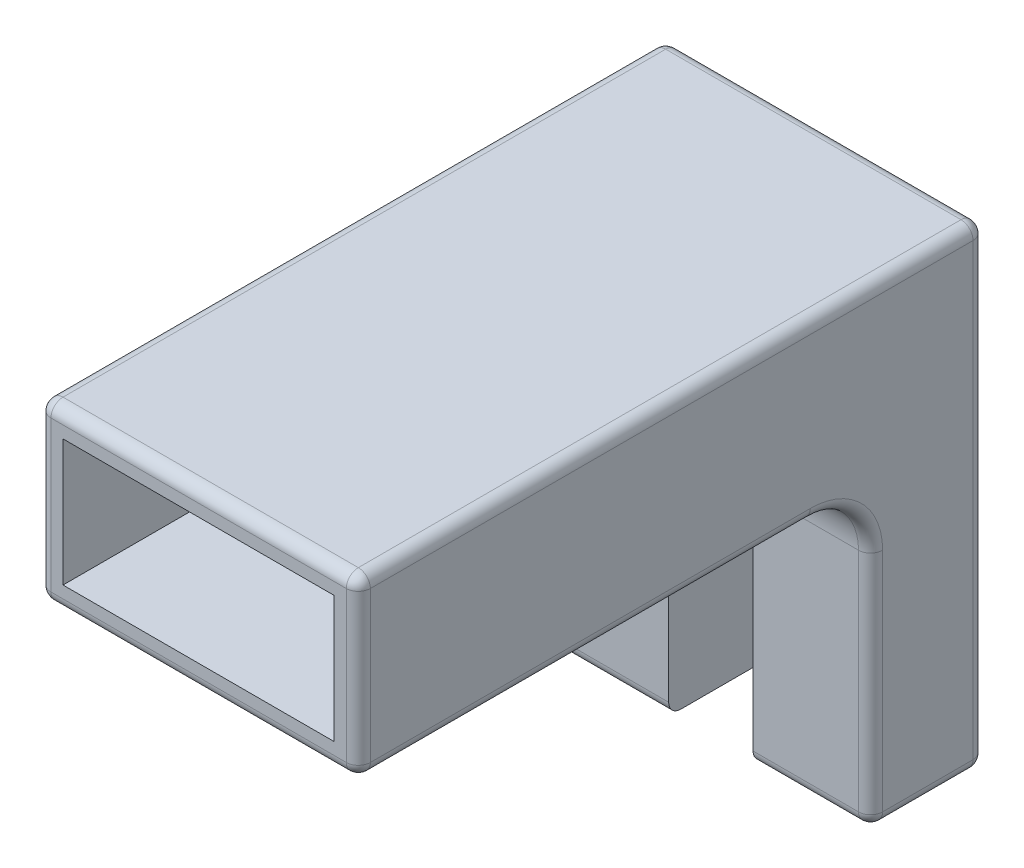
SolidWorks part; units mm, degrees
ref_plane "正面" through (0, 0, 0) normal (0, 0, 1) x (1, 0, 0)
ref_plane "平面" through (0, 0, 0) normal (0, 1, 0) x (1, 0, 0)
ref_plane "右側面" through (0, 0, 0) normal (1, 0, 0) x (0, 0, -1)
sketch "ｽｹｯﾁ2" plane through (0, 0, 0) normal (0, 0, 1) x (1, 0, 0)
  line L1 (0, 0) -> (26.5, 0)
  line L2 (0, 0) -> (0, 14.5)
  line L3 (0, 14.5) -> (26.5, 14.5)
  line L4 (26.5, 0) -> (26.5, 14.5)
  dimension "D1" = 14.5
  dimension "D2" = 26.5
extrude "ﾎﾞｽ - 押し出し1" add sketch "ｽｹｯﾁ2" along normal blind 52
sketch "ｽｹｯﾁ6" plane through (0, 0, 52) normal (0, 0, 1) x (1, 0, 0)
  line L0 (26.5, 14.5) -> (0, 14.5) construction
  line L1 (2, 12.5) -> (24.5, 12.5)
  line L2 (2, 12.5) -> (2, 2)
  line L3 (2, 2) -> (24.5, 2)
  line L4 (24.5, 12.5) -> (24.5, 2)
  line L5 (0, 14.5) -> (0, 0) construction
  dimension "D1" = 10.5
  dimension "D2" = 22.5
  dimension "D3" = 2
  dimension "D4" = 2
extrude "ｶｯﾄ - 押し出し1" cut sketch "ｽｹｯﾁ6" against normal blind 49
sketch "ｽｹｯﾁ7" plane through (0, 0, 0) normal (0, -1, 0) x (1, 0, 0)
  line L0 (26.5, 52) -> (26.5, 0) construction
  line L1 (0, 0) -> (26.5, 0)
  line L2 (0, 0) -> (0, 9.5)
  line L3 (0, 9.5) -> (26.5, 9.5)
  line L4 (26.5, 0) -> (26.5, 9.5)
  dimension "D1" = 9.5
extrude "ﾎﾞｽ - 押し出し2" add sketch "ｽｹｯﾁ7" along normal blind 24.8
fillet "ﾌｨﾚｯﾄ1" radius 5 1 edges at (13.25, 0, 9.5)
fillet "ﾌｨﾚｯﾄ2" radius 1 1 edges at (26.5, 14.5, 26)
fillet "ﾌｨﾚｯﾄ4" radius 1 7 edges at (12.75, 14.5, 0) (26.2071, 14.2071, 0) (26.5, -5.65, 0) (26.5, -24.8, 4.75) (26.5, -14.9, 9.5) (26.5, -1.4645, 10.9645) (26.5, 0, 33.25)
fillet "ﾌｨﾚｯﾄ5" radius 1 11 edges at (0, 14.2071, 0.2929) (26.2071, -24.5071, 0.2929) (26.2071, -24.5071, 9.2071) (0, 14.5, 26.5) (0, -5.65, 0) (0, 0, 33.25) (0, -1.4645, 10.9645) (0, -14.9, 9.5) (0, -24.8, 4.75) (12.75, -24.8, 0) (12.75, -24.8, 9.5)
fillet "ﾌｨﾚｯﾄ6" radius 1 8 edges at (26.2071, 0.2929, 52) (26.2071, 14.2071, 52) (0.2929, 14.2071, 52) (0.2929, 0.2929, 52) (26.5, 7.25, 52) (13.25, 14.5, 52) (13.25, 0, 52) (0, 7.25, 52)
sketch "ｽｹｯﾁ8" plane through (0, -24.8, 0) normal (0, -1, 0) x (1, 0, 0)
  line L0 (1, 9.5) -> (25.5, 9.5) construction
  line L1 (9.75, 9.5) -> (16.75, 9.5)
  line L2 (9.75, 9.5) -> (9.75, 0)
  line L3 (9.75, 0) -> (16.75, 0)
  line L4 (16.75, 9.5) -> (16.75, 0)
  line L5 (25.5, 0) -> (1, 0) construction
  line L7 (13.25, 9.5) -> (13.25, 0) construction
  line L8 (0, 1) -> (0, 8.5) construction
  dimension "D1" = 9.5
  dimension "D2" = 7
  dimension "D3" = 13.25
  dimension "D4" = 3.5
extrude "ｶｯﾄ - 押し出し2" cut sketch "ｽｹｯﾁ8" against normal blind 20
